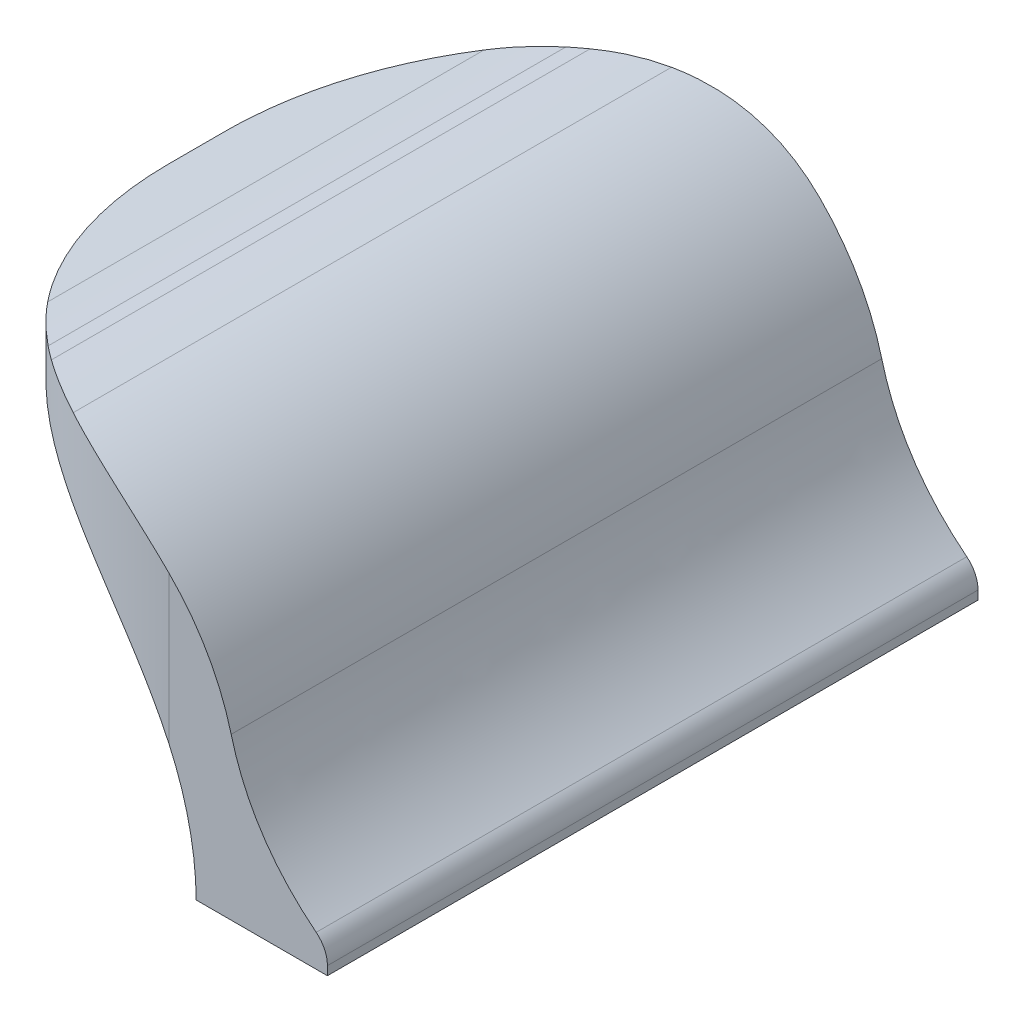
SolidWorks part; units mm, degrees
ref_plane "Front Plane" through (0, 0, 0) normal (0, 0, 1) x (1, 0, 0)
ref_plane "Top Plane" through (0, 0, 0) normal (0, 1, 0) x (1, 0, 0)
ref_plane "Right Plane" through (0, 0, 0) normal (1, 0, 0) x (0, 0, -1)
sketch "Sketch1" plane through (0, 0, 0) normal (0, 1, 0) x (1, 0, 0)
  line L1 (50.8, -109.5375) -> (-50.8, -109.5375)
  line L2 (50.8, -109.5375) -> (50.8, 109.5375)
  line L3 (50.8, 109.5375) -> (-50.8, 109.5375)
  line L4 (-50.8, -109.5375) -> (-50.8, 109.5375)
  line L5 (50.8, -109.5375) -> (-50.8, 109.5375) construction
  line L6 (50.8, 109.5375) -> (-50.8, -109.5375) construction
  point P0 (0, 0)
  dimension "D1" = 219.075
  dimension "D2" = 101.6
extrude "Boss-Extrude2" add sketch "Sketch1" along normal blind 114.3
sketch "Sketch2" plane through (0, 0, 109.5375) normal (0, 0, 1) x (1, 0, 0)
  line L0 (-19.7624, 0) -> (-82.5846, 0) construction
  line L1 (-50.8, 0) -> (50.8, 0) construction
  circle A0 centre (-73.196, 0) radius 101.6
extrude "Cut-Extrude1" cut sketch "Sketch2" against normal up to surface (219.075 mm away) up to face at (0, 57.15, -109.5375)
fillet "Fillet1" radius 90 1 edges at (50.8, 114.3, 0)
sketch "Sketch3" plane through (0, 0, 109.5375) normal (0, 0, 1) x (1, 0, 0)
  line L1 (37.4088, 71.5344) -> (72.5715, 71.5344)
  line L2 (37.4088, 71.5344) -> (37.4088, 0)
  line L3 (37.4088, 0) -> (72.5715, 0)
  line L4 (72.5715, 71.5344) -> (72.5715, 0)
  arc A0 (50.8, 24.3) -> (-39.2, 114.3) centre (-39.2, 24.3) ccw construction
  dimension "D1" = 71.5344
extrude "Boss-Extrude3" add sketch "Sketch3" against normal up to surface (219.075 mm away) up to face at (4.202, 64.0869, -109.5375)
sketch "Sketch4" plane through (0, 0, 109.5375) normal (0, 0, 1) x (1, 0, 0)
  line L0 (72.5715, 0) -> (72.5715, 71.5344) construction
  line L1 (37.4088, 71.5344) -> (72.5715, 71.5344)
  line L2 (72.5715, 71.5344) -> (72.5715, 7.9172)
  spline S0 degree 2 poles (37.4088, 71.5344) (40.1599, 31.2727) (72.5715, 7.9172) knots 0 0 0 1 1 1
extrude "Cut-Extrude2" cut sketch "Sketch4" against normal blind 219.3
fillet "Fillet2" radius 80 1 edges
fillet "Fillet3" radius 10 1 edges at (72.5715, 7.9172, 0)
sketch "Sketch5" plane through (0, 0, 109.5375) normal (0, 0, 1) x (1, 0, 0)
  line L0 (-80.8, 99.1008) -> (-80.8, 110.1008)
  line L1 (-80.8, 110.1008) -> (-50.8, 114.3)
  line L3 (-50.8, 114.3) -> (-50.8, 99.1008)
  line L4 (-50.8, 99.1008) -> (-80.8, 99.1008)
  dimension "D1" = 11
extrude "Boss-Extrude5" add sketch "Sketch5" against normal up to surface (219.075 mm away) up to face at (13.7293, 61.5601, -109.5375)
fillet "Fillet5" radius 100 1 edges at (-50.8, 99.1008, 0)
fillet "Fillet7" radius 100 1 edges at (-50.8, 114.3, 0)
fillet "Fillet11" radius 100 6 edges at (-50.7832, 114.0583, -109.5375) (-41.5177, 114.3, -109.5375) (-69.2487, 111.7177, -109.5375) (-80.8, 104.6008, -109.5375) (-76.196, 99.1008, -109.5375)
fillet "Fillet12" radius 100 6 edges at (-69.2487, 111.7177, 109.5375) (-50.7832, 114.0583, 109.5375) (-30.4727, 113.8759, 109.5375) (-80.8, 104.6008, 109.5375) (-76.196, 99.1008, 109.5375) (-41.5177, 114.3, 109.5375)
